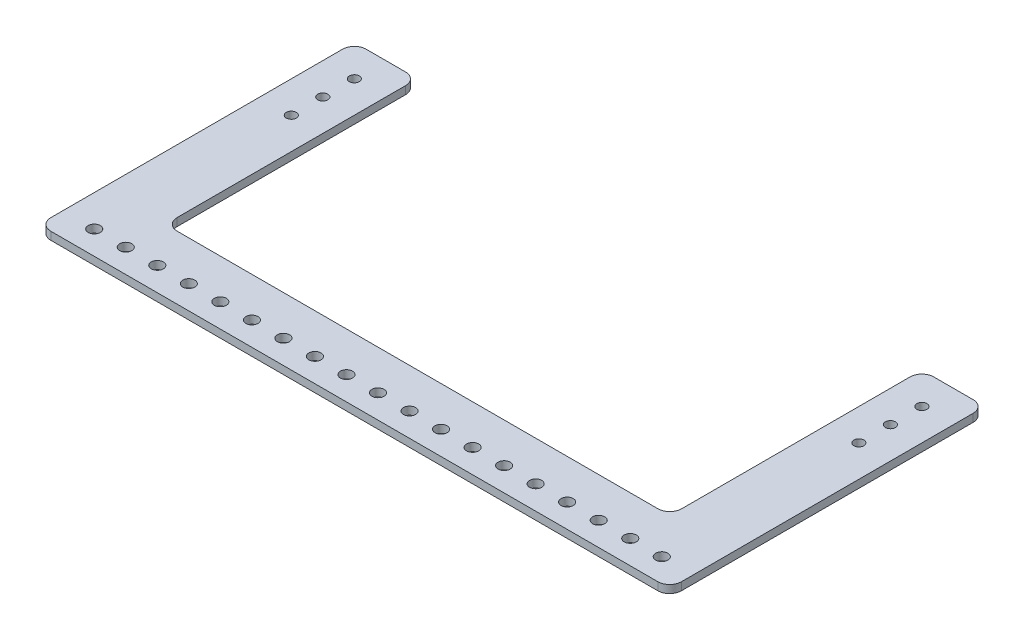
SolidWorks part; units mm, degrees
material "6061-T6 (SS)"
ref_plane "Front Plane" through (0, 0, 0) normal (0, 0, 1) x (1, 0, 0)
ref_plane "Top Plane" through (0, 0, 0) normal (0, 1, 0) x (1, 0, 0)
ref_plane "Right Plane" through (0, 0, 0) normal (1, 0, 0) x (0, 0, -1)
sketch "Sketch2" plane through (0, 0, 0) normal (0, 1, 0) x (1, 0, 0)
  line L0 (0, 63.5) -> (0, -63.5) construction
  line L1 (-127, -63.5) -> (127, -63.5)
  line L2 (-127, -63.5) -> (-127, 63.5)
  line L3 (-127, 63.5) -> (127, 63.5)
  line L4 (127, -63.5) -> (127, 63.5)
  line L5 (-127, -63.5) -> (127, 63.5) construction
  line L6 (-127, 63.5) -> (127, -63.5) construction
  line L7 (-101.6, 63.5) -> (101.6, 63.5)
  line L8 (-101.6, 63.5) -> (-101.6, -38.0365)
  line L9 (-101.6, -38.0365) -> (101.6, -38.0365)
  line L10 (101.6, 63.5) -> (101.6, -38.0365)
  line L11 (127, 63.5) -> (101.6, 63.5) construction
  line L12 (127, 63.5) -> (127, -38.0365) construction
  line L13 (127, -38.0365) -> (101.6, -38.0365) construction
  line L14 (101.6, 63.5) -> (101.6, -38.0365) construction
  circle A0 centre (-114.3, 50.8) radius 2.0193
  circle A1 centre (-114.3, 38.1) radius 2.0193
  circle A2 centre (-114.3, 25.4) radius 2.0193
  circle A6 centre (114.3, 25.4) radius 2.0193
  circle A7 centre (114.3, 38.1) radius 2.0193
  circle A8 centre (114.3, 50.8) radius 2.0193
  point P0 (0, 0)
  point P10 (0, -38.0365)
  point P11 (0, -63.5)
  dimension "D8" = 4.0386
  dimension "D1" = 254
  dimension "D2" = 127
  dimension "D3" = 203.2
  dimension "D4" = 25.4635
  dimension "D5" = 12.7
  dimension "D6" = 12.7
  dimension "D7" = 12.7
  dimension "D9" = 12.7
extrude "Boss-Extrude1" add sketch "Sketch2" along normal blind 3.175 contours L3 L10 L9 L8 L2 L1 L4 A7 A0 A1 A2 A6 A8 region at (-124.1602, 0, 0)
fillet "Fillet1" radius 4.7625 8 edges at (127, 1.5875, -63.5) (-127, 1.5875, 63.5) (-127, 1.5875, -63.5) (-101.6, 1.5875, -63.5) (-101.6, 1.5875, 38.0365) (101.6, 1.5875, 38.0365) (101.6, 1.5875, -63.5) (127, 1.5875, 63.5)
sketch "Sketch3" plane through (0, 3.175, 0) normal (0, 1, 0) x (1, 0, 0)
  line L0 (-127, -58.7375) -> (-127, 58.7375) construction
  line L1 (-122.2375, -63.5) -> (122.2375, -63.5) construction
  line L2 (0, -38.0365) -> (0, -63.5) construction
  line L3 (-96.8375, -38.0365) -> (96.8375, -38.0365) construction
  line L4 (127, -58.7375) -> (127, 58.7375) construction
  circle A0 centre (-114.3, -53.975) radius 2.4384
  circle A1 centre (-101.6, -53.975) radius 2.4384
  circle A2 centre (-88.9, -53.975) radius 2.4384
  circle A3 centre (-76.2, -53.975) radius 2.4384
  circle A4 centre (-63.5, -53.975) radius 2.4384
  circle A5 centre (-50.8, -53.975) radius 2.4384
  circle A6 centre (-38.1, -53.975) radius 2.4384
  circle A7 centre (-25.4, -53.975) radius 2.4384
  circle A8 centre (-12.7, -53.975) radius 2.4384
  circle A9 centre (0, -53.975) radius 2.4384
  circle A10 centre (12.7, -53.975) radius 2.4384
  circle A11 centre (25.4, -53.975) radius 2.4384
  circle A12 centre (38.1, -53.975) radius 2.4384
  circle A13 centre (50.8, -53.975) radius 2.4384
  circle A14 centre (63.5, -53.975) radius 2.4384
  circle A15 centre (76.2, -53.975) radius 2.4384
  circle A16 centre (88.9, -53.975) radius 2.4384
  circle A17 centre (101.6, -53.975) radius 2.4384
  circle A18 centre (114.3, -53.975) radius 2.4384
  dimension "D1" = 4.8768
  dimension "D2" = 12.7
  dimension "D3" = 9.525
  dimension "D4" = 12.7
  dimension "D5" = 12.7
  dimension "D7" = 12.7
  dimension "D6" = 17
extrude "Cut-Extrude1" cut sketch "Sketch3" against normal through all
